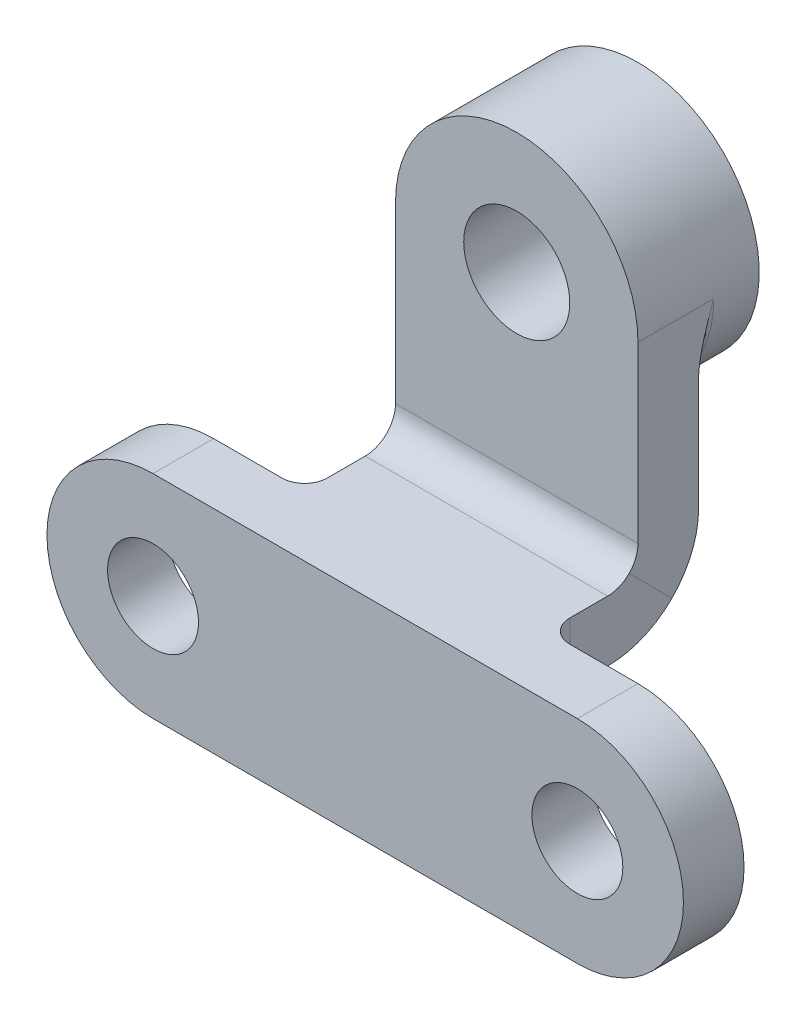
SolidWorks part; units mm, degrees
ref_plane "Front Plane" through (0, 0, 0) normal (0, 0, 1) x (1, 0, 0)
ref_plane "Top Plane" through (0, 0, 0) normal (0, 1, 0) x (1, 0, 0)
ref_plane "Right Plane" through (0, 0, 0) normal (1, 0, 0) x (0, 0, -1)
sketch "Sketch2" plane through (0, 0, 0) normal (0, 0, 1) x (1, 0, 0)
  line L0 (-35, 0) -> (35, 0) construction
  line L1 (-35, 17.5) -> (35, 17.5)
  line L2 (-35, -17.5) -> (35, -17.5)
  arc A0 (-35, 17.5) -> (-35, -17.5) centre (-35, 0) ccw
  arc A1 (35, -17.5) -> (35, 17.5) centre (35, 0) ccw
  circle A2 centre (-35, 0) radius 7.5
  circle A3 centre (35, 0) radius 7.5
  point P3 (0, 0)
  dimension "D2" = 17.5
  dimension "D3" = 35
  dimension "D4" = 15
  dimension "D5" = 15
  dimension "D1" = 70
extrude "Boss-Extrude1" add sketch "Sketch2" along normal blind 10
sketch "Sketch3" plane through (0, 0, 0) normal (0, 0, -1) x (-1, 0, 0)
  line L0 (-35, 17.5) -> (35, 17.5) construction
  line L1 (-20, 17.5) -> (20, 17.5)
  line L2 (-20, 17.5) -> (-20, 7.5)
  line L3 (-20, 7.5) -> (20, 7.5)
  line L4 (20, 17.5) -> (20, 7.5)
  line L5 (0, 0) -> (0, 35.5852) construction
  dimension "D1" = 40
  dimension "D2" = 10
  dimension "D3" = 20
sketch "Sketch4" plane through (0, 0, 0) normal (1, 0, 0) x (0, 0, -1)
  line L0 (0, 17.5) -> (0, 7.5) construction
  line L1 (0, 12.5) -> (20, 12.5)
  line L2 (20, 12.5) -> (20, 72.5)
  dimension "D1" = 20
  dimension "D2" = 60
sweep "Sweep1" add profiles "Sketch3" path "Sketch4"
fillet "Fillet1" radius 5 1 edges at (0, 17.5, -15)
fillet "Fillet2" radius 15 1 edges at (0, 7.5, -25)
sketch "Sketch5" plane through (0, 0, -25) normal (0, 0, -1) x (-1, 0, 0)
  line L0 (-42.5, 0) -> (42.5, 0) construction
  line L1 (0, 0) -> (0, 51.25) construction
  circle A0 centre (-35, 0) radius 7.5 construction
  circle A1 centre (35, 0) radius 7.5 construction
  circle A2 centre (0, 51.25) radius 20
  circle A3 centre (0, 51.25) radius 8.75
  line M3 (-20, 72.5) -> (-20, 22.5)
  line M5 (20, 22.5) -> (20, 72.5)
  line M6 (20, 72.5) -> (-20, 72.5)
  dimension "D1" = 40
  dimension "D3" = 17.5
  dimension "D2" = 51.25
extrude "Cut-Extrude1" cut sketch "Sketch5" against normal blind 10 contours A2 M5 M6 M3 region at (0, 71.7029, -25)
extrude "Boss-Extrude2" add sketch "Sketch5<3>" along normal blind 10
sketch "Sketch5<3>" plane through (0, 0, -25) normal (0, 0, -1) x (-1, 0, 0) same geometry as "Sketch5"
extrude "Cut-Extrude2" cut sketch "Sketch5<4>" against normal blind 10 contours A3
sketch "Sketch5<4>" plane through (0, 0, -25) normal (0, 0, -1) x (-1, 0, 0) same geometry as "Sketch5"
fillet "Fillet3" radius 2.5 1 edges at (0, 31.25, -25)
fillet "Fillet4" radius 3.75 2 edges at (-20, 12.5, 0) (20, 12.5, 0)
fillet "Fillet5" radius 2.5 1 edges at (0, 7.5, 0)
